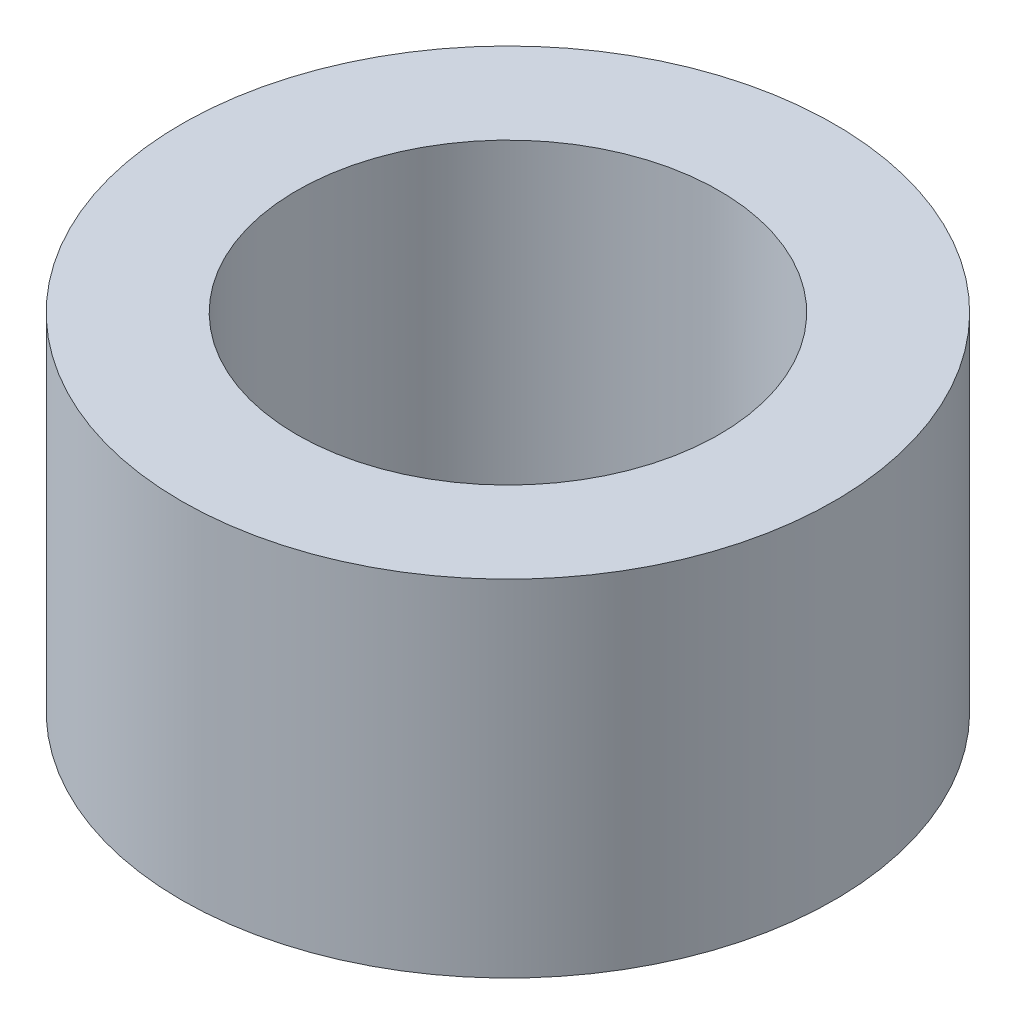
SolidWorks part; units mm, degrees
ref_plane "Front Plane" through (0, 0, 0) normal (0, 0, 1) x (1, 0, 0)
ref_plane "Top Plane" through (0, 0, 0) normal (0, 1, 0) x (1, 0, 0)
ref_plane "Right Plane" through (0, 0, 0) normal (1, 0, 0) x (0, 0, -1)
sketch "Sketch1" plane through (0, 0, 0) normal (0, 1, 0) x (1, 0, 0)
  circle A0 centre (0, 0) radius 15
  dimension "SLEEVE_OD" = 30
extrude "Boss-Extrude1" add sketch "Sketch1" along normal blind 15.87
sketch "Sketch2" plane through (0, 0, 0) normal (0, 1, 0) x (1, 0, 0)
  circle A0 centre (0, 0) radius 9.7057
  dimension "BORE_D" = 19.4115
extrude "Cut-Extrude1" cut sketch "Sketch2" along normal through all
chamfer "Chamfer1" distance 2.5075 angle 60 rebuild error yes
